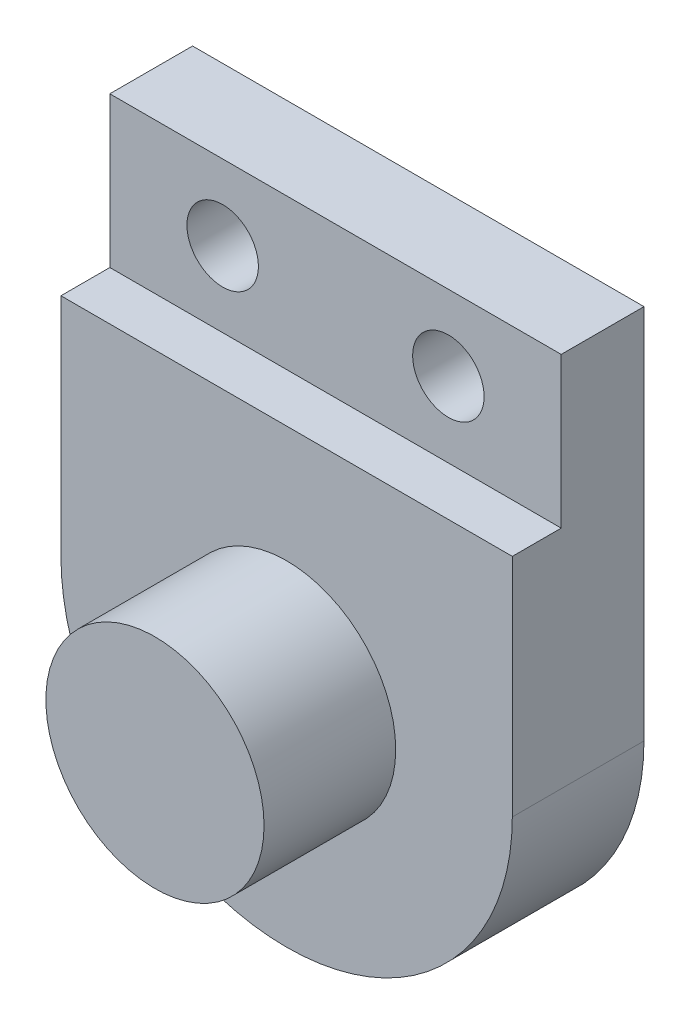
SolidWorks part; units mm, degrees
note: The reader was unsure of these and kept them because the rebuilt part matched: shared geometry of "草图1<4>", "草图1<5>", "草图1<7>".
ref_plane "前视基准面" through (0, 0, 0) normal (0, 0, 1) x (1, 0, 0)
ref_plane "上视基准面" through (0, 0, 0) normal (0, 1, 0) x (1, 0, 0)
ref_plane "右视基准面" through (0, 0, 0) normal (1, 0, 0) x (0, 0, -1)
sketch "草图1" plane through (0, 0, 0) normal (0, 0, 1) x (1, 0, 0)
  line L0 (0, 0) -> (12, 0)
  line L1 (12, 0) -> (12, -6)
  line L2 (6.01, -12) -> (6, -12)
  line L3 (0, -6) -> (0, 0)
  line L4 (12, 0) -> (12, 4)
  line L5 (12, 4) -> (0, 4)
  line L6 (0, 4) -> (0, 0)
  line L7 (12, 2) -> (0, 2) construction
  line L8 (6, 3.5) -> (6, -8.9) construction
  line L9 (6, -12) -> (6, -1012) construction
  circle A0 centre (3, 2) radius 0.95
  circle A1 centre (9, 2) radius 0.95
  circle A4 centre (6, -6) radius 2.9
  arc A5 (12, -6) -> (0, -6) centre (6, -6) cw
  point P8 (12, 2)
  point P15 (6, 4)
  point P21 (12, -12)
  dimension "D4" = 1.9
  dimension "D6" = 6
  dimension "D7" = 6
  dimension "D8" = 5.8
  dimension "D1" = 12
  dimension "D2" = 12
  dimension "D3" = 4
  dimension "D5" = 6
extrude "凸台-拉伸1" add sketch "草图1" along normal blind 3
extrude "凸台-拉伸2" add sketch "草图1<4>" along normal blind 2.2 contours L5 L6 L0 L4 A1 A0
sketch "草图1<4>" plane through (0, 0, 0) normal (0, 0, 1) x (1, 0, 0) same geometry as "草图1"
extrude "凸台-拉伸3" add sketch "草图1<5>" along normal blind 6 contours A4
sketch "草图1<5>" plane through (0, 0, 0) normal (0, 0, 1) x (1, 0, 0) same geometry as "草图1"
sketch "草图2" plane through (0, 0, 0) normal (0, 0, -1) x (-1, 0, 0)
  circle A0 centre (-9, 2) radius 1.85
  circle A1 centre (-3, 2) radius 1.85
extrude "切除-拉伸1" cut sketch "草图2" against normal blind 0.3
ref_plane "基准面1" through (0, 0, 3) normal (0, 0, 1) x (1, 0, 0)
sketch "草图4" plane through (0, 0, 3) normal (0, 0, 1) x (1, 0, 0)
  line L0 (0, 0) -> (12, 0)
  line L1 (12, 0) -> (12, -6)
  line L2 (0, 0) -> (0, -6)
  arc A0 (0, -6) -> (12, -6) centre (6, -6) ccw
  arc A1 (6.01, -12) -> (12, -6) centre (6, -6) ccw construction
extrude "凸台-拉伸4" add sketch "草图4" along normal blind 0.5
extrude "凸台-拉伸6" add sketch "草图1<7>" along normal blind 7 contours A4
sketch "草图1<7>" plane through (0, 0, 0) normal (0, 0, 1) x (1, 0, 0) same geometry as "草图1"
